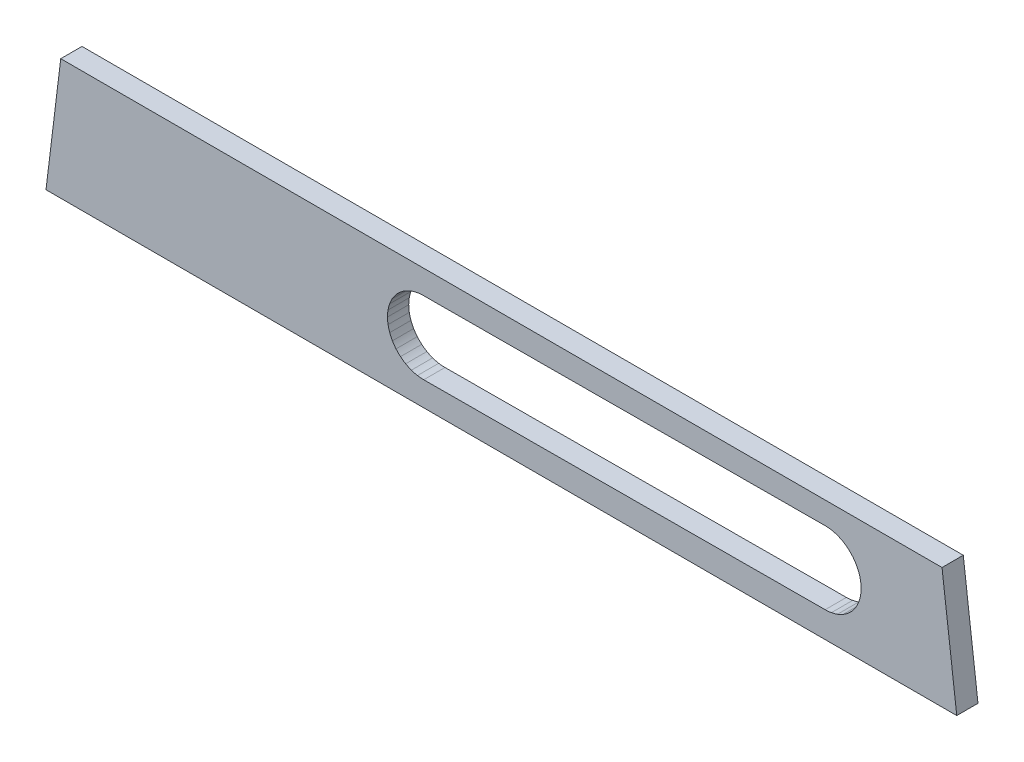
SolidWorks part; units mm, degrees
ref_plane "Front Plane" through (0, 0, 0) normal (0, 0, 1) x (1, 0, 0)
ref_plane "Top Plane" through (0, 0, 0) normal (0, 1, 0) x (1, 0, 0)
ref_plane "Right Plane" through (0, 0, 0) normal (1, 0, 0) x (0, 0, -1)
ref_axis "Axis1" through (0, -55, 0) along (0, 1, 0)
sketch "Model" plane through (0, 0, 0) normal (0, 0, 1) x (1, 0, 0)
  line L8 (28.5954, 208.0794) -> (457.4024, 208.0794)
  line L9 (457.4024, 208.0794) -> (450.4651, 265.0028)
  line L10 (450.4651, 265.0028) -> (35.5326, 265.0028)
  line L11 (35.5326, 265.0028) -> (28.5954, 208.0794)
  line L12 (395.311, 254.5381) -> (206.3133, 253.7973)
  line L13 (206.4476, 219.5423) -> (395.4453, 220.283)
  arc A0 (395.4453, 220.283) -> (398.3962, 220.5548) centre (395.3788, 237.1618) ccw
  arc A1 (398.3962, 220.5548) -> (401.2555, 221.3387) centre (395.3731, 237.1874) ccw
  arc A2 (401.2555, 221.3387) -> (403.9362, 222.611) centre (395.3559, 237.2294) ccw
  arc A3 (403.9362, 222.611) -> (406.3568, 224.3329) centre (395.3244, 237.2795) ccw
  arc A4 (406.3568, 224.3329) -> (408.4439, 226.4522) centre (395.2802, 237.3284) ccw
  arc A5 (408.4439, 226.4522) -> (410.1339, 228.9045) centre (395.2465, 237.3562) ccw
  arc A6 (410.1339, 228.9045) -> (411.3757, 231.6152) centre (395.1958, 237.3871) ccw
  arc A7 (411.3757, 231.6152) -> (412.1313, 234.502) centre (395.1533, 237.4038) ccw
  arc A8 (412.1313, 234.502) -> (412.3779, 237.4772) centre (395.1275, 237.4092) ccw
  arc A9 (412.3779, 237.4772) -> (412.108, 240.4503) centre (395.1236, 237.4095) ccw
  arc A10 (412.108, 240.4503) -> (411.3297, 243.3311) centre (395.1425, 237.4126) ccw
  arc A11 (411.3297, 243.3311) -> (410.0668, 246.032) centre (395.1801, 237.4253) ccw
  arc A12 (410.0668, 246.032) -> (408.3576, 248.4709) centre (395.2289, 237.4518) ccw
  arc A13 (408.3576, 248.4709) -> (406.254, 250.5738) centre (395.2796, 237.492) ccw
  arc A14 (406.254, 250.5738) -> (403.8199, 252.2767) centre (395.3354, 237.5583) ccw
  arc A15 (403.8199, 252.2767) -> (401.1293, 253.5279) centre (395.3617, 237.6069) ccw
  arc A16 (401.1293, 253.5279) -> (398.264, 254.2894) centre (395.3742, 237.6444) ccw
  arc A17 (398.264, 254.2894) -> (395.311, 254.5381) centre (395.3771, 237.6631) ccw
  arc A18 (206.3133, 253.7973) -> (203.3624, 253.5256) centre (206.3798, 236.9186) ccw
  arc A19 (203.3624, 253.5256) -> (200.5031, 252.7416) centre (206.3855, 236.893) ccw
  arc A20 (200.5031, 252.7416) -> (197.8224, 251.4694) centre (206.4027, 236.851) ccw
  arc A21 (197.8224, 251.4694) -> (195.4018, 249.7474) centre (206.4342, 236.8009) ccw
  arc A22 (195.4018, 249.7474) -> (193.3147, 247.6281) centre (206.4784, 236.752) ccw
  arc A23 (193.3147, 247.6281) -> (191.6246, 245.1759) centre (206.5121, 236.7241) ccw
  arc A24 (191.6246, 245.1759) -> (190.3829, 242.4652) centre (206.5628, 236.6933) ccw
  arc A25 (190.3829, 242.4652) -> (189.6273, 239.5784) centre (206.6053, 236.6765) ccw
  arc A26 (189.6273, 239.5784) -> (189.3807, 236.6032) centre (206.6311, 236.6711) ccw
  arc A27 (189.3807, 236.6032) -> (189.6506, 233.63) centre (206.635, 236.6708) ccw
  arc A28 (189.6506, 233.63) -> (190.4288, 230.7492) centre (206.6161, 236.6678) ccw
  arc A29 (190.4288, 230.7492) -> (191.6918, 228.0483) centre (206.5785, 236.655) ccw
  arc A30 (191.6918, 228.0483) -> (193.401, 225.6094) centre (206.5297, 236.6285) ccw
  arc A31 (193.401, 225.6094) -> (195.5046, 223.5065) centre (206.479, 236.5884) ccw
  arc A32 (195.5046, 223.5065) -> (197.9387, 221.8036) centre (206.4232, 236.5221) ccw
  arc A33 (197.9387, 221.8036) -> (200.6293, 220.5524) centre (206.3969, 236.4734) ccw
  arc A34 (200.6293, 220.5524) -> (203.4946, 219.7909) centre (206.3844, 236.4359) ccw
  arc A35 (203.4946, 219.7909) -> (206.4476, 219.5423) centre (206.3815, 236.4172) ccw
extrude "Boss-Extrude1" add sketch "Model" along normal blind 10
